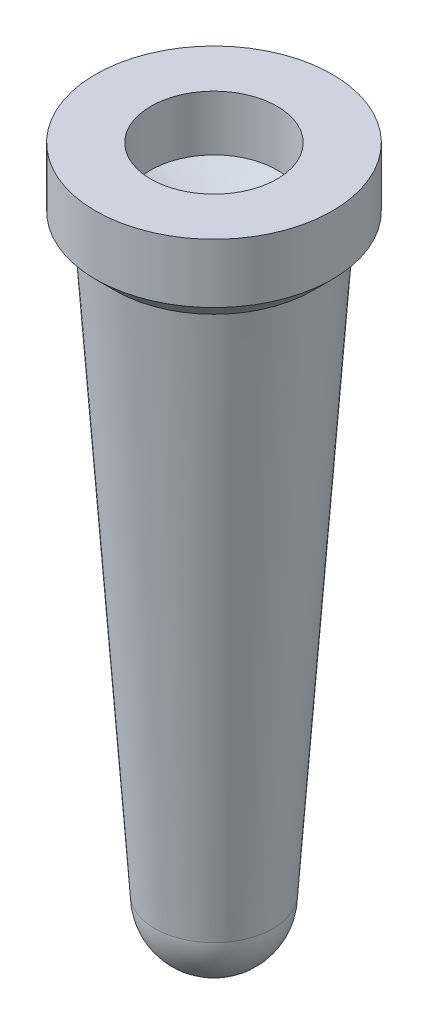
SolidWorks part; units mm, degrees
ref_plane "Front Plane" through (0, 0, 0) normal (0, 0, 1) x (1, 0, 0)
ref_plane "Top Plane" through (0, 0, 0) normal (0, 1, 0) x (1, 0, 0)
ref_plane "Right Plane" through (0, 0, 0) normal (1, 0, 0) x (0, 0, -1)
sketch "Sketch1" plane through (0, 0, 0) normal (0, 1, 0) x (1, 0, 0)
  circle A0 centre (0, 0) radius 0.381
extrude "Boss-Extrude1" add sketch "Sketch1" along normal blind 0.254
chamfer "Chamfer1" distance 0.0635 angle 45 1 edges at (0, 0, 0.381)
ref_axis "Axis1" through (0, 0.254, 0) along (0, -1, 0)
sketch "Sketch3" plane through (0, 0.254, 0) normal (0, 1, 0) x (1, 0, 0)
  line L0 (0.381, 0) -> (-0.381, 0) construction
  circle A0 centre (0, 0) radius 0.381 construction
ref_plane "Plane1" through (-0.381, 0, 0) normal (-1, 0, 0) x (0, 0, 1)
ref_plane "Plane2" through (0.381, 0, 0) normal (1, 0, 0) x (0, 0, -1)
ref_plane "Plane3" through (0, 0, 0) normal (-1, 0, 0) x (0, 0, 1)
sketch "Sketch4" plane through (0, 0, 0) normal (-1, 0, 0) x (0, 0, 1)
  line L0 (0, -1.8415) -> (0.1905, -1.8415) construction
  line L1 (0, -2.032) -> (0, -1.8415) construction
  line L2 (0, 0) -> (0, -2.032)
  line L3 (0, 0) -> (0.3175, 0)
  line L4 (0.3175, 0) -> (0.1905, -1.8415)
  arc A0 (0, -2.032) -> (0.1905, -1.8415) centre (0, -1.8415) ccw
revolve "Revolve1" add sketch "Sketch4" angle 360 about axis through (0, 0.254, 0) along (0, -1, 0)
sketch "Sketch5" plane through (0, 0.254, 0) normal (0, 1, 0) x (1, 0, 0)
  circle A0 centre (0, 0) radius 0.2032
extrude "Cut-Extrude1" cut sketch "Sketch5" against normal blind 0.254
chamfer "Chamfer2" distance 0.0762 angle 69.444 1 edges at (0, 0, 0.2032) first distance on face at (0, 0, 0.2032)
